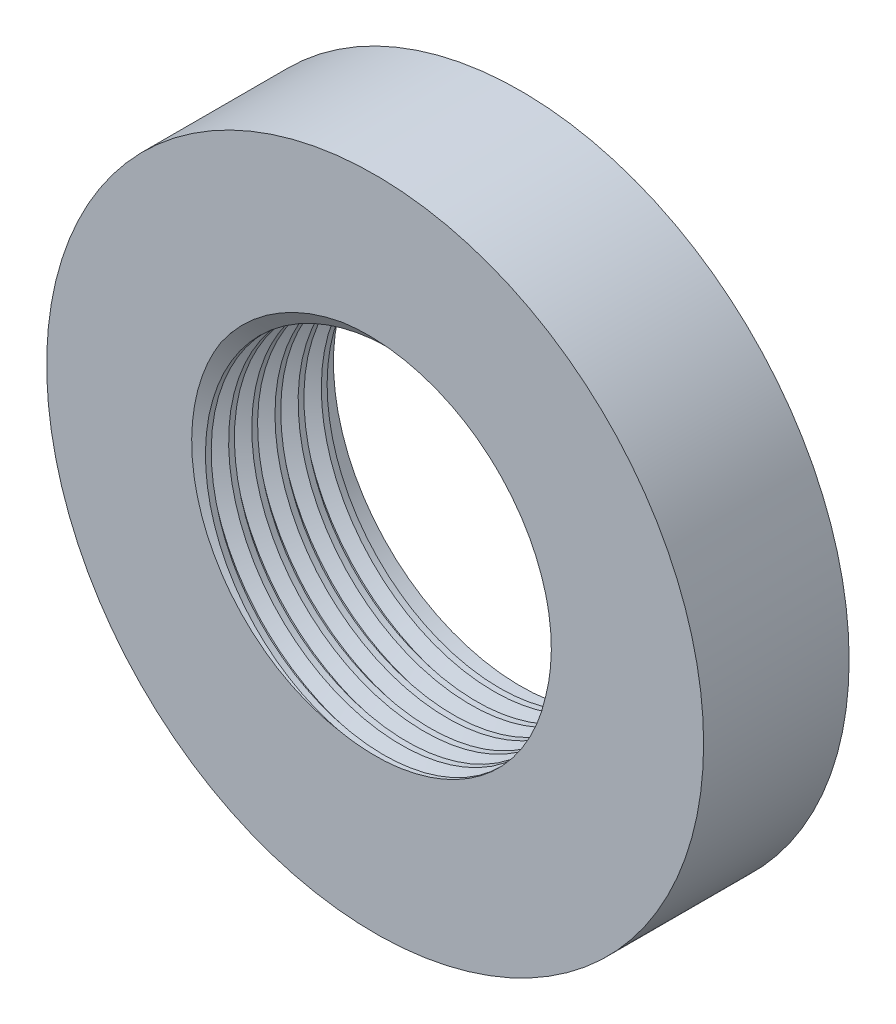
SolidWorks part; units mm, degrees
material "1023 Carbon Steel Sheet (SS)"
ref_plane "Front Plane" through (0, 0, 0) normal (0, 0, 1) x (1, 0, 0)
ref_plane "Top Plane" through (0, 0, 0) normal (0, 1, 0) x (1, 0, 0)
ref_plane "Right Plane" through (0, 0, 0) normal (1, 0, 0) x (0, 0, -1)
sketch "Sketch1" plane through (0, 0, 0) normal (0, 0, 1) x (1, 0, 0)
  circle A0 centre (0, 0) radius 20
extrude "Boss-Extrude1" add sketch "Sketch1" along normal blind 8.86
sketch "Sketch2" plane through (0, 0, 0) normal (0, 0, 1) x (1, 0, 0)
  circle A0 centre (0, 0) radius 11.4
extrude "Cut-Extrude1" cut sketch "Sketch2" along normal blind 27.86
thread "Thread1" pitch 1.4111 method extrude profile "Thread Profile1" start angle 0, offset 0, length 0, pitch 1.4111, diameter 22.8
ref_plane "Plane1" through (11.4, 0, 0) normal (0, -1, 0) x (1, 0, 0)
sketch "Thread Profile1" plane through (11.4, 0, 0) normal (0, -1, 0) x (1, 0, 0)
  line L0 (0, 0) -> (0, 1.4111) construction
  line L11 (0, 0) -> (0, 1.2347)
  line L12 (0, 1.2347) -> (-0.7638, 0.7937)
  line L13 (-0.7638, 0.7937) -> (-0.7638, 0.441)
  line L15 (-0.7638, 0.441) -> (0, 0)
  line L17 (-0.7638, 0.6174) -> (0, 0.6174) construction
  point P2 (0, 0)
  dimension "Pitch" = 1.4111
  dimension "Profile_Angle" = 60
  dimension "Profile_Land" = 0.3528
  dimension "Profile_Height" = 0.7638
ref_plane "Plane2" through (0, 0, 8.86) normal (0, 0, 1) x (1, 0, 0)
sketch "Sketch8" plane through (0, 0, 8.86) normal (0, 0, 1) x (1, 0, 0)
  circle A0 centre (0, 0) radius 17.165
extrude "Cut-Extrude2" cut sketch "Sketch8" along normal through all
